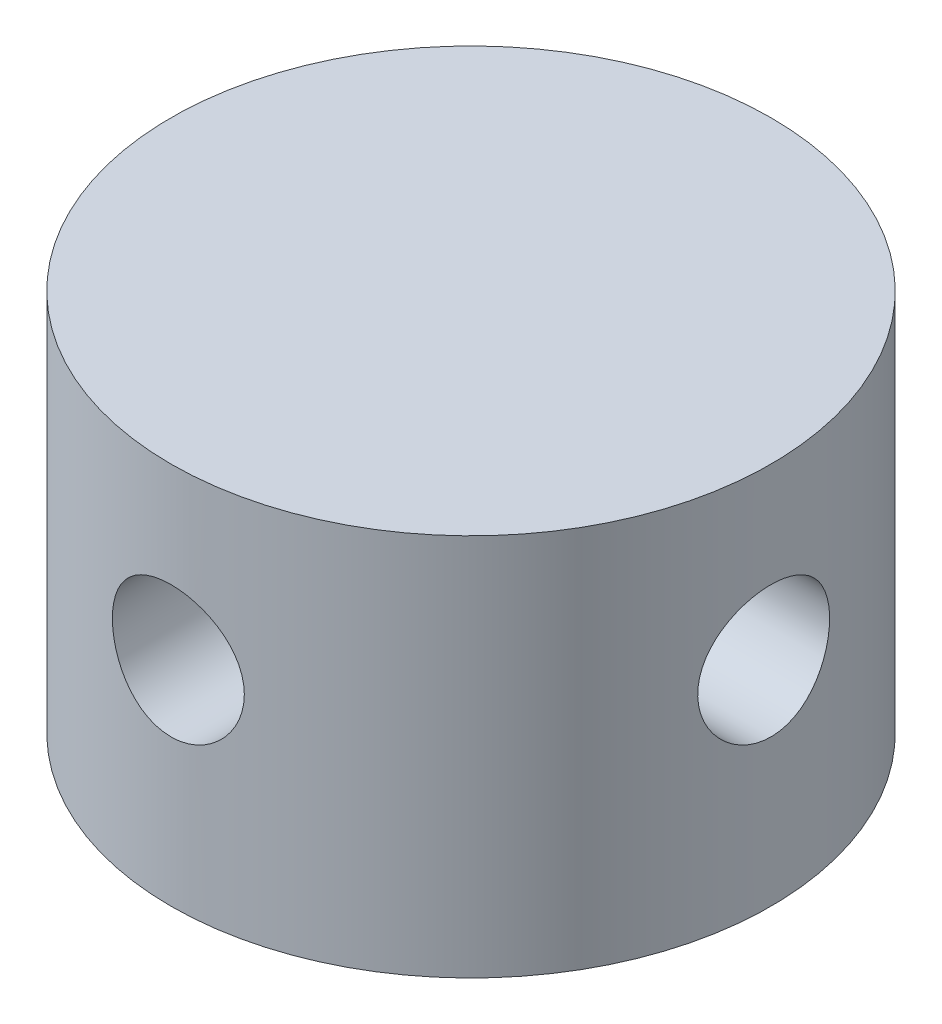
SolidWorks part; units mm, degrees
ref_plane "Front Plane" through (0, 0, 0) normal (0, 0, 1) x (1, 0, 0)
ref_plane "Top Plane" through (0, 0, 0) normal (0, 1, 0) x (1, 0, 0)
ref_plane "Right Plane" through (0, 0, 0) normal (1, 0, 0) x (0, 0, -1)
sketch "Sketch1" plane through (0, 0, 0) normal (0, 1, 0) x (1, 0, 0)
  circle A0 centre (0, 0) radius 14.1
  dimension "D1" = 28.2
extrude "Boss-Extrude1" add sketch "Sketch1" along normal blind 18
ref_plane "Plane1" through (14.1, 0, 0) normal (1, 0, 0) x (0, 0, -1)
ref_axis "Axis1" through (0, 18, 0) along (0, -1, 0)
sketch "Sketch2" plane through (14.1, 0, 0) normal (1, 0, 0) x (0, 0, -1)
  line L0 (0, 19.9907) -> (0, 0) construction
  line L1 (0, 18) -> (0, 0) construction
  circle A0 centre (0, 9.9954) radius 3.1
  dimension "D1" = 6.2
extrude "Cut-Extrude1" cut sketch "Sketch2" against normal blind 9
pattern_circular "CirPattern1" count 4 over 360 about axis through (0, 18, 0) along (0, -1, 0) of "Cut-Extrude1"
